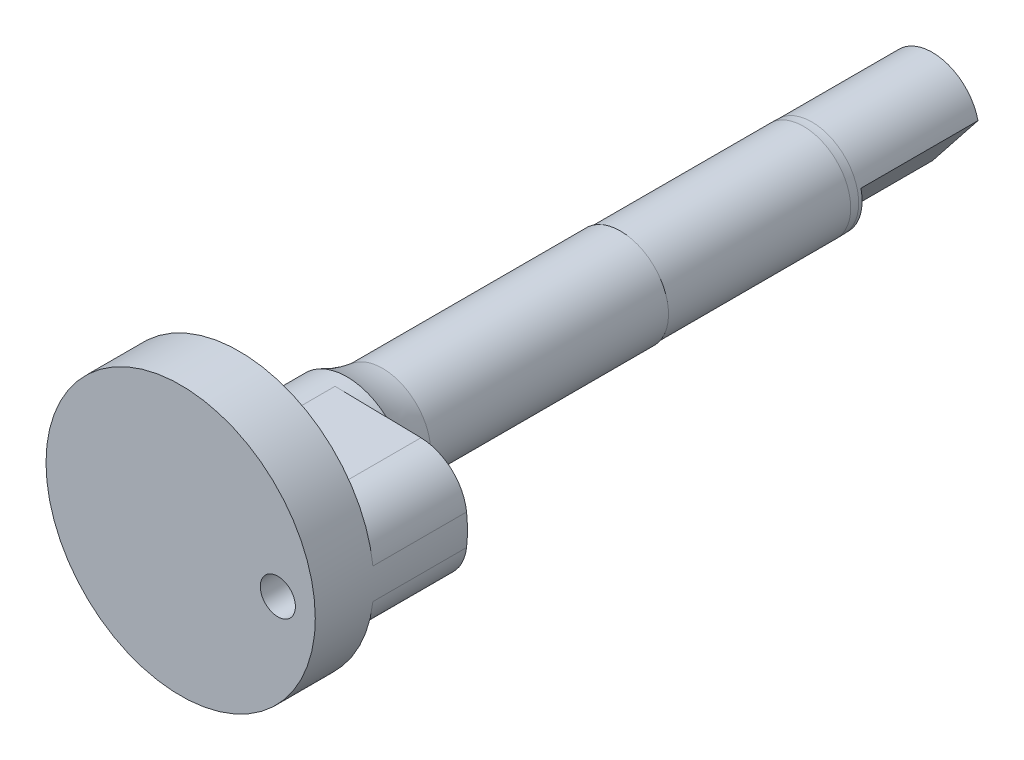
SolidWorks part; units mm, degrees
ref_plane "Front Plane" through (0, 0, 0) normal (0, 0, 1) x (1, 0, 0)
ref_plane "Top Plane" through (0, 0, 0) normal (0, 1, 0) x (1, 0, 0)
ref_plane "Right Plane" through (0, 0, 0) normal (1, 0, 0) x (0, 0, -1)
sketch "Sketch1" plane through (0, 0, 0) normal (0, 0, 1) x (1, 0, 0)
  circle A0 centre (0, 0) radius 5
  dimension "D1" = 10
extrude "Boss-Extrude1" add sketch "Sketch1" along normal blind 100
sketch "Sketch2" plane through (0, 0, 100) normal (0, 0, 1) x (1, 0, 0)
  circle A0 centre (0, 0) radius 11.5
  dimension "D1" = 23
extrude "Boss-Extrude2" add sketch "Sketch2" along normal blind 5
sketch "Sketch3" plane through (0, 0, 105) normal (0, 0, 1) x (1, 0, 0)
  circle A0 centre (8.3029, 0) radius 1.5
  dimension "D1" = 3
extrude "Boss-Extrude3" add sketch "Sketch3" along normal blind 5
sketch "Sketch4" plane through (0, 0, 105) normal (0, 0, 1) x (1, 0, 0)
  point P0 (0, 0)
sketch "Sketch5" plane through (0, 0, 100) normal (0, 0, -1) x (-1, 0, 0)
  line L0 (-10.45, 4.8007) -> (0, 5)
  line L1 (-10.45, -4.8007) -> (-0.0958, -4.9991)
  arc A0 (-10.45, 4.8007) -> (-10.45, -4.8007) centre (0, 0) ccw
  arc A3 (-0.0958, -4.9991) -> (0, 5) centre (0, 0) ccw
  dimension "D2" = 23
extrude "Boss-Extrude4" add sketch "Sketch5" along normal blind 8
sketch "Sketch6" plane through (0, 0, 92) normal (0, 0, -1) x (-1, 0, 0)
  line L0 (-0.1906, 4.9964) -> (-10.45, 4.8007) construction
  line L1 (-10.45, -4.8007) -> (-0.0958, -4.9991) construction
  line L2 (-7.5274, -4.8567) -> (-10.45, -4.8007)
  line L4 (-6.3506, 4.7029) -> (-7.079, 4.3955)
  arc A0 (-11.4246, -1.3148) -> (-7.5274, -4.8567) centre (-7.4508, -0.8575) ccw
  arc A1 (-6.3506, 4.7029) -> (-11.4246, 1.3144) centre (-7.4509, 0.8572) ccw
  arc A2 (-10.45, 4.8007) -> (-10.45, -4.8007) centre (0, 0) ccw construction
  arc A3 (-11.1877, 2.6616) -> (-11.4246, 1.3144) centre (0, 0) ccw
  arc A4 (-11.4246, -1.3148) -> (-10.45, -4.8007) centre (0, 0) ccw
  line M2 (-0.1906, 4.9964) -> (-10.45, 4.8007)
  arc M3 (-10.45, 4.8007) -> (-10.45, -4.8007) centre (0, 0) ccw
  dimension "D1" = 8
  dimension "D2" = 8
extrude "Cut-Extrude2" cut sketch "Sketch6" against normal blind 8 contours A1 M2 M3 | A0 L2 A4 region at (10.1318, 4.0806, 92)
sketch "Sketch7" plane through (-96.4802, -4.6204, 77.4174) normal (0.9133, 0.4072, 0) x (0.4072, -0.9133, 0)
  line L1 (29.8682, 11.6259) -> (43.292, 11.6259)
  line L2 (29.8682, 11.6259) -> (29.8682, 77.4174)
  line L3 (29.8682, 77.4174) -> (43.292, 77.4174)
  line L4 (43.292, 11.6259) -> (43.292, 77.4174)
extrude "Cut-Extrude4" cut sketch "Sketch7" against normal through all both and the other way through all
sketch "Sketch8" plane through (0, 0, 110) normal (0, 0, 1) x (1, 0, 0)
  circle A0 centre (8.3029, 0) radius 1.5
extrude "Cut-Extrude5" cut sketch "Sketch8" against normal through all both and the other way through all
sketch "Sketch9" plane through (0, 0, 65.7915) normal (0, 0, -1) x (-1, 0, 0)
  circle A0 centre (0, 0) radius 5
  circle A1 centre (0, 0) radius 4.025
extrude "Cut-Extrude6" cut sketch "Sketch9" against normal blind 25
fillet "Fillet1" radius 10 1 edges at (0, 4.025, 90.7915)
sketch "Sketch10" plane through (0, 0, 65.7915) normal (0, 0, -1) x (-1, 0, 0)
  circle A0 centre (0, 0) radius 4.025
  circle A1 centre (0, 0) radius 4.025 construction
extrude "Boss-Extrude5" add sketch "Sketch10" along normal blind 25
sketch "Sketch11" plane through (0, 0, 40.7915) normal (0, 0, -1) x (-1, 0, 0)
  line L0 (-3.9186, 0.9194) -> (0, -4.025)
  circle A0 centre (0, 0) radius 4.025
  circle A1 centre (0, 0) radius 4.025 construction
  circle M2 centre (0, 0) radius 4.025
  dimension "D1" = 2.5
extrude "Cut-Extrude7" cut sketch "Sketch11" against normal blind 10 contours L0 M2 region at (2.4461, -1.9386, 40.7915)
sketch "Sketch12" plane through (0, 0, 40.7915) normal (0, 0, -1) x (-1, 0, 0)
  circle A0 centre (0, 0) radius 4.025
  arc A1 (0, -4.025) -> (-3.9186, 0.9194) centre (0, 0) ccw construction
  circle A2 centre (0, 0) radius 4
  dimension "D1" = 8
extrude "Cut-Extrude8" cut sketch "Sketch12" against normal blind 11
fillet "Fillet2" radius 10 1 edges at (0, 4, 51.7915)
sketch "Sketch13" plane through (0, 0, 72.432) normal (0, 0, -1) x (-1, 0, 0)
  circle A0 centre (0, 0) radius 4.025
  circle A1 centre (0, 0) radius 4.025 construction
  circle A2 centre (0, 0) radius 4.105
  dimension "D1" = 0.08
extrude "Boss-Extrude6" add sketch "Sketch13" against normal blind 20
sketch "Sketch14" plane through (0, 0, 72.432) normal (0, 0, -1) x (-1, 0, 0)
  circle A0 centre (0, 0) radius 4.105
  circle A1 centre (0, 0) radius 4.105 construction
extrude "Boss-Extrude7" add sketch "Sketch14" along normal blind 5
